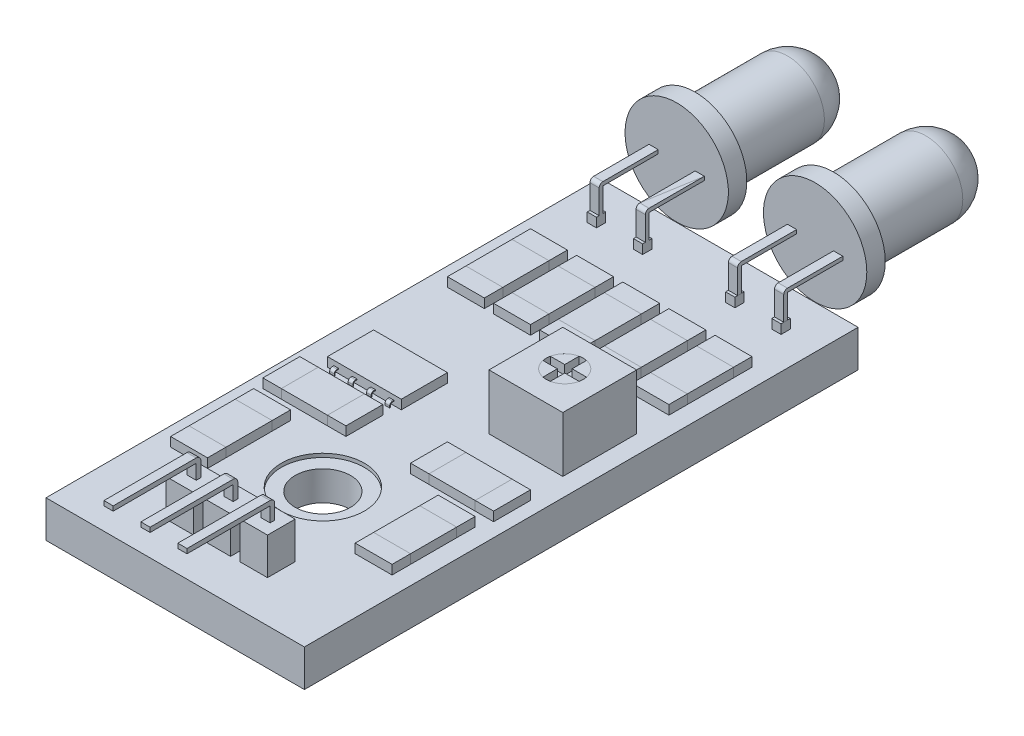
SolidWorks part; units mm, degrees
ref_plane "Alzado" through (0, 0, 0) normal (0, 0, 1) x (1, 0, 0)
ref_plane "Planta" through (0, 0, 0) normal (0, 1, 0) x (1, 0, 0)
ref_plane "Vista lateral" through (0, 0, 0) normal (1, 0, 0) x (0, 0, -1)
sketch "Croquis1" plane through (0, 0, 0) normal (0, 1, 0) x (1, 0, 0)
  line L1 (-7, 15) -> (7, 15)
  line L2 (-7, 15) -> (-7, -15)
  line L3 (-7, -15) -> (7, -15)
  line L4 (7, 15) -> (7, -15)
  line L5 (-7, 15) -> (7, -15) construction
  line L6 (-7, -15) -> (7, 15) construction
  point P0 (0, 0)
  dimension "D1" = 14
  dimension "D2" = 30
extrude "Saliente-Extruir1" add sketch "Croquis1" along normal mid plane 2
sketch "Croquis2" plane through (0, 1, 0) normal (0, 1, 0) x (1, 0, 0)
  circle A0 centre (0, -7) radius 1.5
  dimension "D1" = 3
  dimension "D2" = 7
extrude "Cortar-Extruir1" cut sketch "Croquis2" against normal blind 2
sketch "Croquis3" plane through (0, 1, 0) normal (0, 1, 0) x (1, 0, 0)
  circle A0 centre (0, -7) radius 2.25
  dimension "D1" = 4.5
extrude "Cortar-Extruir2" cut sketch "Croquis3" against normal blind 0.2
mirror "Simetría1" about plane through (0, 0, 0) normal (0, 1, 0) of "Cortar-Extruir2"
sketch "Croquis4" plane through (0, 1, 0) normal (0, 1, 0) x (1, 0, 0)
  line L0 (-3, -13) -> (-1, -11) construction
  line L1 (-3, -13) -> (3, -13)
  line L2 (-3, -13) -> (-3, -11)
  line L3 (-3, -11) -> (3, -11)
  line L4 (3, -13) -> (3, -11)
  line L5 (-3, -13) -> (3, -11) construction
  line L6 (-3, -11) -> (3, -13) construction
  line L7 (-1, -13) -> (1, -13)
  line L8 (-1, -13) -> (-1, -11)
  line L9 (-1, -11) -> (1, -11)
  line L10 (1, -13) -> (1, -11)
  line L11 (-1, -13) -> (1, -11) construction
  line L12 (-1, -11) -> (1, -13) construction
  line L13 (-1, -13) -> (-3, -11) construction
  line L14 (1, -11) -> (3, -13) construction
  line L15 (1, -13) -> (3, -11) construction
  line L17 (-2.75, -12.75) -> (-1.25, -12.75)
  line L18 (-2.75, -12.75) -> (-2.75, -11.25)
  line L19 (-2.75, -11.25) -> (-1.25, -11.25)
  line L20 (-1.25, -12.75) -> (-1.25, -11.25)
  line L21 (-2.75, -12.75) -> (-1.25, -11.25) construction
  line L22 (-2.75, -11.25) -> (-1.25, -12.75) construction
  line L23 (-0.75, -12.75) -> (0.75, -12.75)
  line L24 (-0.75, -12.75) -> (-0.75, -11.25)
  line L25 (-0.75, -11.25) -> (0.75, -11.25)
  line L26 (0.75, -12.75) -> (0.75, -11.25)
  line L27 (-0.75, -12.75) -> (0.75, -11.25) construction
  line L28 (-0.75, -11.25) -> (0.75, -12.75) construction
  line L29 (1.25, -12.75) -> (2.75, -12.75)
  line L30 (1.25, -12.75) -> (1.25, -11.25)
  line L31 (1.25, -11.25) -> (2.75, -11.25)
  line L32 (2.75, -12.75) -> (2.75, -11.25)
  line L33 (1.25, -12.75) -> (2.75, -11.25) construction
  line L34 (1.25, -11.25) -> (2.75, -12.75) construction
  point P0 (0, -12)
  point P5 (0, -12)
  point P11 (-2, -12)
  point P16 (0, -12)
  point P21 (2, -12)
  dimension "D1" = 6
  dimension "D2" = 2
  dimension "D3" = 12
  dimension "D4" = 2
  dimension "D5" = 1.5
  dimension "D6" = 1.5
  dimension "D7" = 1.5
extrude "Saliente-Extruir2" add sketch "Croquis4" along normal blind 2 contours L17 L20 L19 L18 | L23 L26 L25 L24 | L29 L32 L31 L30 region at (-2, 1, 12) region at (0, 1, 12) region at (2, 1, 12)
sketch "Croquis5" plane through (2.75, 0, 0) normal (1, 0, 0) x (0, 0, -1)
  line L0 (-11.8602, 3) -> (-11.8602, 3.8)
  line L1 (-12.75, 3) -> (-11.25, 3) construction
  line L2 (-12.1102, 4.05) -> (-16.6102, 4.05)
  line L3 (-16.6102, 4.05) -> (-16.6102, 3.8)
  line L4 (-16.6102, 3.8) -> (-12.1102, 3.8)
  line L5 (-12.1102, 3.8) -> (-12.1102, 3)
  line L6 (-12.1102, 3) -> (-11.8602, 3)
  arc A0 (-11.8602, 3.8) -> (-12.1102, 4.05) centre (-12.1102, 3.8) ccw
  dimension "D3" = 0.25
  dimension "D1" = 4.5
  dimension "D2" = 0.8
extrude "Saliente-Extruir3" add sketch "Croquis5" along normal mid plane 0.5 from offset 0.75 separate body offset against normal yes
pattern_linear "MatrizL1" count 3 spacing 2 along (-1, 0, 0) of "Saliente-Extruir3"
sketch "Croquis6" plane through (0, 1, 0) normal (0, 1, 0) x (1, 0, 0)
  line L1 (4, -4.7499) -> (6, -4.7499)
  line L2 (4, -4.7499) -> (4, -9.2499)
  line L3 (4, -9.2499) -> (6, -9.2499)
  line L4 (6, -4.7499) -> (6, -9.2499)
  line L5 (4, -4.7499) -> (6, -9.2499) construction
  line L6 (4, -9.2499) -> (6, -4.7499) construction
  line L7 (4, -5.7499) -> (6, -5.7499)
  line L8 (4, -5.7499) -> (4, -8.2499)
  line L9 (4, -8.2499) -> (6, -8.2499)
  line L10 (6, -5.7499) -> (6, -8.2499)
  line L11 (4, -5.7499) -> (6, -8.2499) construction
  line L12 (4, -8.2499) -> (6, -5.7499) construction
  circle A0 centre (0, -7) radius 2.25 construction
  circle A1 centre (0, -7) radius 1.5 construction
  point P0 (5, -6.9999)
  point P7 (5, -6.9999)
  dimension "D3" = 6
  dimension "D1" = 4.5
  dimension "D2" = 2
  dimension "D4" = 2.5
  dimension "D5" = 0.0001
extrude "Saliente-Extruir4" add sketch "Croquis6" along normal blind 0.5 separate body contours L2 L9 L4 L7 region at (5, 1, 6.9999)
extrude "Saliente-Extruir5" add sketch "Croquis6<3>" along normal blind 0.5 separate body contours L9 L2 L3 L4 | L2 L7 L4 L1 region at (5, 1, 5.2499) region at (5, 1, 8.7499)
sketch "Croquis6<3>" plane through (0, 1, 0) normal (0, 1, 0) x (1, 0, 0) same geometry as "Croquis6"
mirror "Simetría14" about plane through (0, 0, 0) normal (1, 0, 0) of bodies 112 109 111
sketch "Croquis8" plane through (0, 1, 0) normal (0, 1, 0) x (1, 0, 0)
  line L1 (1.75, -2) -> (6.25, -2)
  line L2 (1.75, -2) -> (1.75, -4)
  line L3 (1.75, -4) -> (6.25, -4)
  line L4 (6.25, -2) -> (6.25, -4)
  line L5 (1.75, -2) -> (6.25, -4) construction
  line L6 (1.75, -4) -> (6.25, -2) construction
  line L7 (2.75, -2) -> (5.25, -2)
  line L8 (2.75, -2) -> (2.75, -4)
  line L9 (2.75, -4) -> (5.25, -4)
  line L10 (5.25, -2) -> (5.25, -4)
  line L11 (2.75, -2) -> (5.25, -4) construction
  line L12 (2.75, -4) -> (5.25, -2) construction
  circle A0 centre (0, -7) radius 1.5 construction
  point P0 (4, -3)
  point P7 (4, -3)
  point P12 (5.25, -3)
  dimension "D1" = 3
  dimension "D2" = 2
  dimension "D3" = 4
  dimension "D4" = 4.5
  dimension "D5" = 2.5
extrude "Saliente-Extruir6" add sketch "Croquis8" along normal blind 0.5 separate body contours L10 L1 L8 L3 region at (4, 1, 3)
extrude "Saliente-Extruir7" add sketch "Croquis8<3>" along normal blind 0.5 separate body contours L8 L1 L2 L3 | L1 L10 L3 L4 region at (2.25, 1, 3) region at (5.75, 1, 3)
sketch "Croquis8<3>" plane through (0, 1, 0) normal (0, 1, 0) x (1, 0, 0) same geometry as "Croquis8"
mirror "Simetría15" about plane through (0, 0, 0) normal (1, 0, 0) of bodies 136 138 137
sketch "Croquis9" plane through (0, 1, 0) normal (0, 1, 0) x (1, 0, 0)
  line L1 (-5.5, 1.25) -> (-1.5, 1.25)
  line L2 (-5.5, 1.25) -> (-5.5, -1.25)
  line L3 (-5.5, -1.25) -> (-1.5, -1.25)
  line L4 (-1.5, 1.25) -> (-1.5, -1.25)
  line L5 (-5.5, 1.25) -> (-1.5, -1.25) construction
  line L6 (-5.5, -1.25) -> (-1.5, 1.25) construction
  point P0 (-3.5, 0)
  dimension "D1" = 4
  dimension "D2" = 3.5
  dimension "D3" = 2.5
extrude "Saliente-Extruir8" add sketch "Croquis9" along normal blind 0.5 separate body
sketch "Croquis10" plane through (-5.5, 0, 0) normal (-1, 0, 0) x (0, 0, 1)
  line L0 (1.25, 1.25) -> (1.33, 1.25)
  line L1 (1.25, 1.5) -> (1.25, 1) construction
  line L2 (1.48, 1.1) -> (1.48, 1)
  line L3 (-15, 1) -> (15, 1) construction
  line L4 (1.48, 1) -> (1.43, 1)
  line L5 (1.43, 1) -> (1.43, 1.1)
  line L6 (1.33, 1.2) -> (1.25, 1.2)
  line L7 (1.25, 1.2) -> (1.25, 1.25)
  line L8 (0, 1) -> (0, 1.7057) construction
  line L9 (-1.48, 1) -> (-1.43, 1)
  line L10 (-1.25, 1.2) -> (-1.25, 1.25)
  line L11 (-1.33, 1.2) -> (-1.25, 1.2)
  line L12 (-1.43, 1) -> (-1.43, 1.1)
  line L13 (-1.48, 1.1) -> (-1.48, 1)
  line L14 (-1.25, 1.25) -> (-1.33, 1.25)
  arc A0 (1.33, 1.25) -> (1.48, 1.1) centre (1.33, 1.1) cw
  arc A1 (1.43, 1.1) -> (1.33, 1.2) centre (1.33, 1.1) ccw
  arc A2 (-1.43, 1.1) -> (-1.33, 1.2) centre (-1.33, 1.1) cw
  arc A3 (-1.33, 1.25) -> (-1.48, 1.1) centre (-1.33, 1.1) ccw
  dimension "D1" = 0.15
  dimension "D4" = 0.1
  dimension "D3" = 0.08
extrude "Saliente-Extruir9" add sketch "Croquis10" along normal blind 0.25 from offset 0.6 separate body offset against normal yes
pattern_linear "MatrizL4" count 4 spacing 1 along (1, 0, 0) of "Saliente-Extruir9"
sketch "Croquis11" plane through (0, 1, 0) normal (0, 1, 0) x (1, 0, 0)
  line L1 (2, 4) -> (6, 4)
  line L2 (2, 4) -> (2, 0)
  line L3 (2, 0) -> (6, 0)
  line L4 (6, 4) -> (6, 0)
  line L5 (2, 4) -> (6, 0) construction
  line L6 (2, 0) -> (6, 4) construction
  point P0 (4, 2)
  dimension "D1" = 4
  dimension "D2" = 4
  dimension "D3" = 2
extrude "Saliente-Extruir10" add sketch "Croquis11" along normal blind 3 separate body
sketch "Croquis12" plane through (0, 4, 0) normal (0, 1, 0) x (1, 0, 0)
  circle A0 centre (4, 2.104) radius 1
  dimension "D1" = 2
extrude "Cortar-Extruir3" cut sketch "Croquis12" against normal blind 1
sketch "Croquis13" plane through (0, 3, 0) normal (0, 1, 0) x (1, 0, 0)
  circle A0 centre (4, 2.104) radius 1 construction
  circle A1 centre (4, 2.104) radius 1
extrude "Saliente-Extruir11" add sketch "Croquis13" along normal blind 0.5 separate body
sketch "Croquis14" plane through (0, 3.5, 0) normal (0, 1, 0) x (1, 0, 0)
  line L0 (4, 3.104) -> (4, 1.104) construction
  line L1 (3, 2.104) -> (5, 2.104) construction
  line L2 (3.8, 3.104) -> (3.8, 1.104)
  line L3 (3, 1.904) -> (5, 1.904)
  line L4 (4.2, 3.104) -> (4.2, 1.104)
  line L5 (3, 2.304) -> (5, 2.304)
  circle A0 centre (4, 2.104) radius 1
  circle M3 centre (4, 2.104) radius 1
  dimension "D1" = 0.2
  dimension "D2" = 0.2
extrude "Saliente-Extruir12" add sketch "Croquis14" along normal blind 0.5 separate body contours L5 L2 M3 | L4 L5 M3 | L3 L4 M3 | L3 L2 M3 region at (3.4887, 3.5, -2.6153) region at (4.5113, 3.5, -2.6153) region at (3.4887, 3.5, -1.5927) region at (4.5113, 3.5, -1.5927)
sketch "Croquis15" plane through (0, 1, 0) normal (0, 1, 0) x (1, 0, 0)
  line L1 (6, 5.75) -> (4, 5.75)
  line L2 (6, 5.75) -> (6, 10.25)
  line L3 (6, 10.25) -> (4, 10.25)
  line L4 (4, 5.75) -> (4, 10.25)
  line L5 (6, 5.75) -> (4, 10.25) construction
  line L6 (6, 10.25) -> (4, 5.75) construction
  line L7 (4, 9.25) -> (6, 9.25)
  line L8 (4, 9.25) -> (4, 6.75)
  line L9 (4, 6.75) -> (6, 6.75)
  line L10 (6, 9.25) -> (6, 6.75)
  line L11 (4, 9.25) -> (6, 6.75) construction
  line L12 (4, 6.75) -> (6, 9.25) construction
  point P0 (5, 8)
  point P5 (5, 8)
  dimension "D1" = 8
  dimension "D2" = 4.5
  dimension "D3" = 2
  dimension "D4" = 4
  dimension "D5" = 2.5
extrude "Saliente-Extruir13" add sketch "Croquis15" along normal blind 0.5 separate body contours L4 L9 L2 L7 region at (5, 1, -8)
extrude "Saliente-Extruir14" add sketch "Croquis15<4>" along normal blind 0.5 separate body contours L9 L4 L1 L2 | L4 L7 L2 L3 region at (5, 1, -6.25) region at (5, 1, -9.75)
sketch "Croquis15<4>" plane through (0, 1, 0) normal (0, 1, 0) x (1, 0, 0) same geometry as "Croquis15"
pattern_linear "MatrizL5" count 5 spacing 2.5 along (-1, 0, 0) of bodies 162 161 163
sketch "Croquis17" plane through (0, 1, 0) normal (0, 1, 0) x (1, 0, 0)
  line L0 (-3.75, 13.8247) -> (-3.75, 11.8247)
  line L1 (-6.25, 11.8247) -> (6.25, 11.8247)
  line L2 (-6.25, 11.8247) -> (-6.25, 13.8247)
  line L3 (-6.25, 13.8247) -> (6.25, 13.8247)
  line L4 (6.25, 11.8247) -> (6.25, 13.8247)
  line L5 (-1.25, 13.8247) -> (-1.25, 11.8247)
  line L6 (1.25, 13.8247) -> (1.25, 11.8247)
  line L7 (3.75, 13.8247) -> (3.75, 11.8247)
  line L8 (-6.25, 13.8247) -> (-3.75, 11.8247) construction
  line L9 (-3.75, 13.8247) -> (-1.25, 11.8247) construction
  line L10 (-1.25, 13.8247) -> (1.25, 11.8247) construction
  line L11 (1.25, 13.8247) -> (3.75, 11.8247) construction
  line L12 (3.75, 13.8247) -> (6.25, 11.8247) construction
  line L13 (3.75, 11.8247) -> (6.25, 13.8247) construction
  line L14 (1.25, 11.8247) -> (3.75, 13.8247) construction
  line L15 (-1.25, 11.8247) -> (1.25, 13.8247) construction
  line L16 (-3.75, 11.8247) -> (-1.25, 13.8247) construction
  line L17 (-3.75, 13.8247) -> (-6.25, 11.8247) construction
  line L19 (-5.25, 13.0747) -> (-4.75, 13.0747)
  line L20 (-5.25, 13.0747) -> (-5.25, 12.5747)
  line L21 (-5.25, 12.5747) -> (-4.75, 12.5747)
  line L22 (-4.75, 13.0747) -> (-4.75, 12.5747)
  line L23 (-5.25, 13.0747) -> (-4.75, 12.5747) construction
  line L24 (-5.25, 12.5747) -> (-4.75, 13.0747) construction
  line L25 (-2.75, 13.0747) -> (-2.25, 13.0747)
  line L26 (-2.75, 13.0747) -> (-2.75, 12.5747)
  line L27 (-2.75, 12.5747) -> (-2.25, 12.5747)
  line L28 (-2.25, 13.0747) -> (-2.25, 12.5747)
  line L29 (-2.75, 13.0747) -> (-2.25, 12.5747) construction
  line L30 (-2.75, 12.5747) -> (-2.25, 13.0747) construction
  line L31 (-0.25, 13.0747) -> (0.25, 13.0747)
  line L32 (-0.25, 13.0747) -> (-0.25, 12.5747)
  line L33 (-0.25, 12.5747) -> (0.25, 12.5747)
  line L34 (0.25, 13.0747) -> (0.25, 12.5747)
  line L35 (-0.25, 13.0747) -> (0.25, 12.5747) construction
  line L36 (-0.25, 12.5747) -> (0.25, 13.0747) construction
  line L37 (2.25, 13.0747) -> (2.75, 13.0747)
  line L38 (2.25, 13.0747) -> (2.25, 12.5747)
  line L39 (2.25, 12.5747) -> (2.75, 12.5747)
  line L40 (2.75, 13.0747) -> (2.75, 12.5747)
  line L41 (2.25, 13.0747) -> (2.75, 12.5747) construction
  line L42 (2.25, 12.5747) -> (2.75, 13.0747) construction
  line L43 (4.75, 13.0747) -> (5.25, 13.0747)
  line L44 (4.75, 13.0747) -> (4.75, 12.5747)
  line L45 (4.75, 12.5747) -> (5.25, 12.5747)
  line L46 (5.25, 13.0747) -> (5.25, 12.5747)
  line L47 (4.75, 13.0747) -> (5.25, 12.5747) construction
  line L48 (4.75, 12.5747) -> (5.25, 13.0747) construction
  point P4 (0, 13.8247)
  point P14 (-3.75, 12.8247)
  point P15 (-5, 12.8247)
  point P20 (-2.5, 12.8247)
  point P25 (0, 12.8247)
  point P30 (2.5, 12.8247)
  point P35 (5, 12.8247)
  dimension "D1" = 12.5
  dimension "D2" = 2
  dimension "D3" = 2.5
  dimension "D4" = 2.5
  dimension "D5" = 2.5
  dimension "D6" = 2.5
  dimension "D7" = 0.5
extrude "Saliente-Extruir15" add sketch "Croquis17" along normal blind 0.5 separate body contours L22 L21 L20 L19 | L28 L27 L26 L25 | L40 L39 L38 L37 | L46 L45 L44 L43
sketch "Croquis18" plane through (5.25, 0, 0) normal (1, 0, 0) x (0, 0, -1)
  line L0 (12.7214, 1.5) -> (12.7214, 2.8)
  line L1 (13.0747, 1.5) -> (12.5747, 1.5) construction
  line L2 (12.9214, 3) -> (15.9214, 3)
  line L3 (15.9214, 3) -> (15.9214, 2.8)
  line L4 (15.9214, 2.8) -> (12.9214, 2.8)
  line L5 (12.9214, 2.8) -> (12.9214, 1.5)
  line L6 (12.9214, 1.5) -> (12.7214, 1.5)
  arc A0 (12.7214, 2.8) -> (12.9214, 3) centre (12.9214, 2.8) cw
  dimension "D2" = 0.2
  dimension "D1" = 3
  dimension "D3" = 1.3
extrude "Saliente-Extruir16" add sketch "Croquis18" along normal mid plane 0.5 from offset 0.25 separate body offset against normal yes
pattern_linear "MatrizL6" count 2 spacing 2.5 along (-1, 0, 0) of "Saliente-Extruir16"
mirror "Simetría16" about plane through (0, 0, 0) normal (1, 0, 0) of "MatrizL6", "Saliente-Extruir16"
ref_plane "Plano13" through (0, 2.9, 0) normal (0, 1, 0) x (1, 0, 0)
sketch "Croquis19" plane through (0, 2.9, 0) normal (0, 1, 0) x (1, 0, 0)
  line L0 (4.75, 15.9214) -> (2.75, 15.9214) construction
  line L1 (2.75, 15.9214) -> (2.75, 12.9214) construction
  line L2 (3.75, 15.9214) -> (3.75, 23.9214) construction
  line L3 (3.75, 15.9214) -> (6.55, 15.9214)
  line L4 (6.55, 15.9214) -> (6.55, 16.9214)
  line L5 (6.55, 16.9214) -> (5.75, 16.9214)
  line L6 (5.75, 16.9214) -> (5.75, 21.9214)
  line L7 (3.75, 15.9214) -> (3.75, 23.9214)
  arc A0 (5.75, 21.9214) -> (3.75, 23.9214) centre (3.75, 21.9214) ccw
  dimension "D2" = 2
  dimension "D1" = 8
  dimension "D3" = 1
  dimension "D4" = 2.8
revolve "Revolución1" add sketch "Croquis19" angle 360 about L7
mirror "Simetría19" about plane through (0, 0, 0) normal (1, 0, 0) of bodies 184 186
